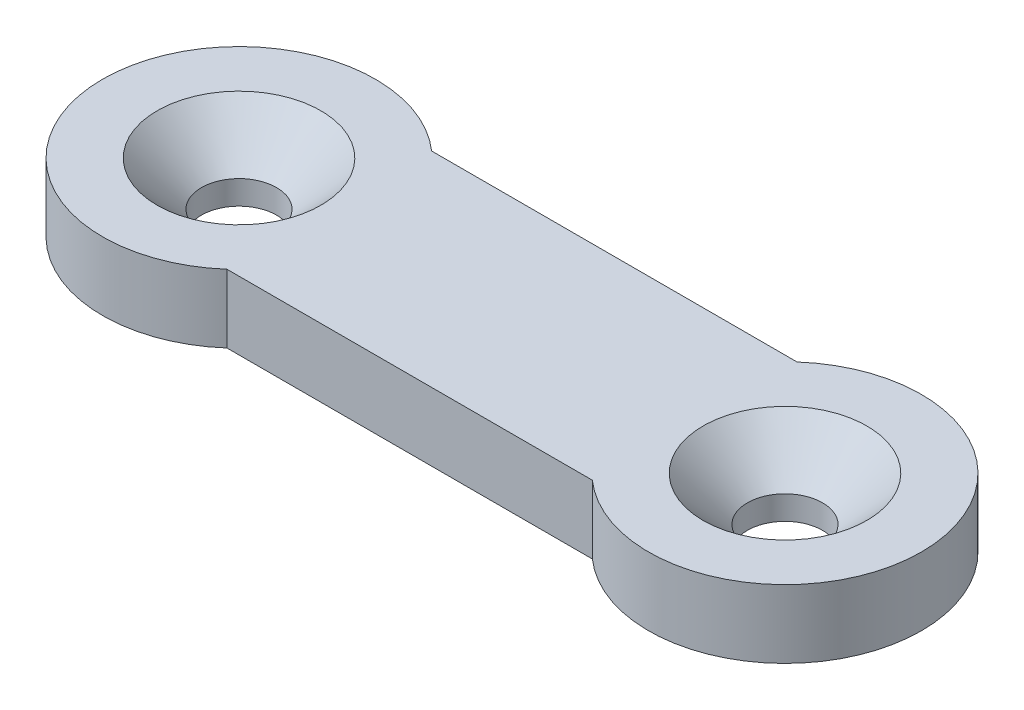
SolidWorks part; units mm, degrees
ref_plane "Front Plane" through (0, 0, 0) normal (0, 0, 1) x (1, 0, 0)
ref_plane "Top Plane" through (0, 0, 0) normal (0, 1, 0) x (1, 0, 0)
ref_plane "Right Plane" through (0, 0, 0) normal (1, 0, 0) x (0, 0, -1)
sketch "Sketch1" plane through (0, 0, 0) normal (0, 1, 0) x (1, 0, 0)
  line L0 (-8, 0) -> (8, 0) construction
  line L1 (-8, 3) -> (8, 3)
  line L2 (-8, -3) -> (8, -3)
  arc A0 (-8, 3) -> (-8, -3) centre (-8, 0) ccw
  arc A1 (8, -3) -> (8, 3) centre (8, 0) ccw
  circle A2 centre (-8, 0) radius 1.1
  circle A5 centre (8, 0) radius 1.1
  point P2 (0, 0)
  dimension "D1" = 2.2
  dimension "D2" = 16
  dimension "D3" = 6
extrude "Boss-Extrude1" add sketch "Sketch1" along normal blind 2
sketch "Sketch3" plane through (0, 2, 0) normal (0, 1, 0) x (1, 0, 0)
  circle A0 centre (-8, 0) radius 4
  circle A1 centre (8, 0) radius 4
  circle A2 centre (-8, 0) radius 1.1
  circle A3 centre (8, 0) radius 1.1
  circle A4 centre (-8, 0) radius 1.1 construction
  circle A5 centre (8, 0) radius 1.1 construction
  dimension "D1" = 8
extrude "Boss-Extrude3" add sketch "Sketch3" against normal up to surface (2 mm away) up to face at (0, 0, 0)
chamfer "Chamfer1" distance 1.3 angle 45 2 edges at (8, 2, 1.1) (-8, 2, 1.1)
